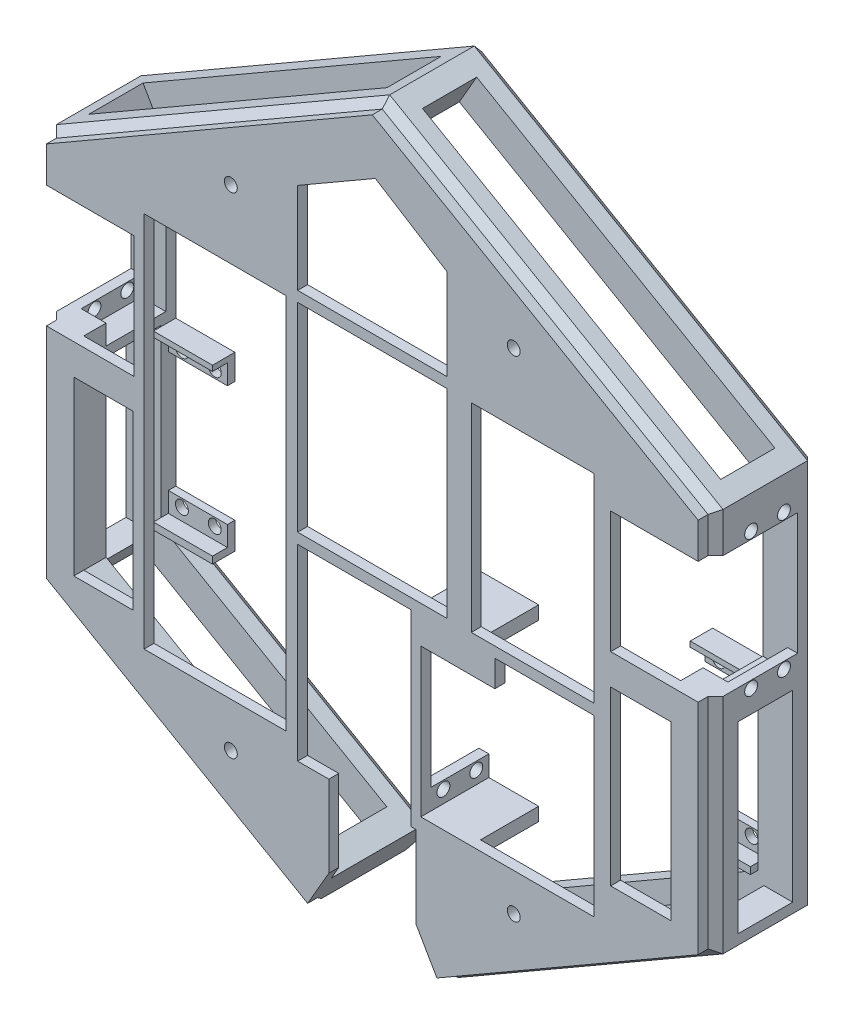
SolidWorks part; units mm, degrees
note: '?' marks a value the reader was unsure of.
material "Caoutchouc"
ref_plane "Plan de face" through (0, 0, 0) normal (0, 0, 1) x (1, 0, 0)
ref_plane "Plan de dessus" through (0, 0, 0) normal (0, 1, 0) x (1, 0, 0)
ref_plane "Plan de droite" through (0, 0, 0) normal (1, 0, 0) x (0, 0, -1)
sketch "Esquisse1" plane through (0, 0, 0) normal (0, 0, 1) x (1, 0, 0)
  line L0 (-67, -38.6825) -> (0, 0)
  line L1 (0, -8.0829) -> (60, -42.7239)
  line L2 (-67, -38.6825) -> (-67, -116.0474)
  line L3 (60, -42.7239) -> (60, -112.006)
  line L4 (67, -38.6825) -> (67, -116.0474)
  line L5 (0, 0) -> (67, -38.6825)
  line L6 (-67, -116.0474) -> (0, -154.7299)
  line L7 (0, -154.7299) -> (67, -116.0474)
  line L8 (60, -112.006) -> (0, -146.647)
  line L9 (0, -146.647) -> (-60, -112.006)
  line L10 (-60, -112.006) -> (-60, -42.7239)
  line L11 (-60, -42.7239) -> (0, -8.0829)
  dimension "D1" = 120
  dimension "D2" = 120
  dimension "D3" = 7
  dimension "D4" = 7
  dimension "D5" = 7
  dimension "D6" = 60
extrude "Boss.-Extru.1" add sketch "Esquisse1" along normal blind 20
chamfer "Chanfrein1" distance 1.5 angle 45 18 edges at (-33.5, -135.3886, 20) (-67, -77.3649, 20) (-33.5, -19.3412, 20) (33.5, -19.3412, 20) (33.5, -135.3886, 20) (67, -77.3649, 20) (-67, -77.3649, 0) (-33.5, -135.3886, 0) (33.5, -135.3886, 0) (67, -77.3649, 0) (33.5, -19.3412, 0) (-33.5, -19.3412, 0) (-30, -129.3265, 0) (30, -129.3265, 0) (60, -77.3649, 0) (30, -25.4034, 0) (-60, -77.3649, 0) (-30, -25.4034, 0)
sketch "Esquisse4" plane through (-60, 0, 0) normal (1, 0, 0) x (0, 0, -1)
  line L0 (-20, -42.7239) -> (-1.5, -42.7239) construction
  line L1 (-1.5, -112.006) -> (-1.5, -42.7239) construction
  line L2 (-3.5, -46.7239) -> (-23.5, -46.7239)
  line L3 (-3.5, -46.7239) -> (-3.5, -71.2239)
  line L4 (-3.5, -71.2239) -> (-23.5, -71.2239)
  line L9 (-23.5, -46.7239) -> (-23.5, -71.2239)
  dimension "D1" = 2
  dimension "D2" = 4
  dimension "D3" = 20
  dimension "D4" = 24.5
extrude "Enlèv. mat.-Extru.1" cut sketch "Esquisse4" against normal blind 10 and the other way through all
ref_plane "Plan1" through (0, 0, 0) normal (1, 0, 0) x (0, 0, -1)
sketch "Esquisse8" plane through (0, 0, 0) normal (-0.5, 0.866, 0) x (0, 0, 1)
  line L0 (18.5, -77.3649) -> (1.5, -77.3649) construction
  line L1 (4.55, -73.3649) -> (15.45, -73.3649)
  line L2 (4.55, -73.3649) -> (4.55, -4.15)
  line L3 (4.55, -4.15) -> (15.45, -4.15)
  line L4 (15.45, -73.3649) -> (15.45, -4.15)
  line L5 (18.5, -77.3649) -> (18.5, 0) construction
  line L6 (1.5, 0) -> (1.5, -77.3649) construction
  line L7 (18.5, 0) -> (1.5, 0) construction
  dimension "D1" = 4
  dimension "D2" = 3.05
  dimension "D3" = 3.05
  dimension "D4" = 4.15
extrude "Enlèv. mat.-Extru.3" cut sketch "Esquisse8" against normal up to surface (7 mm away) up to face at (-30, -25.4034, 10.75)
sketch "Esquisse9" plane through (0, 0, 0) normal (0.5, 0.866, 0) x (0, 0, -1)
  line L0 (-15.45, 2.075) -> (-4.55, 2.075) construction
  line L1 (-15.5, -73.3649) -> (-4.6, -73.3649)
  line L2 (-15.5, -73.3649) -> (-15.5, -4.15)
  line L3 (-15.5, -4.15) -> (-4.6, -4.15)
  line L4 (-4.6, -73.3649) -> (-4.6, -4.15)
  line L6 (-18.5, 0) -> (-1.5, 0) construction
  line L7 (-18.5, 0) -> (-18.5, -77.3649) construction
  line L8 (-18.5, -77.3649) -> (-1.5, -77.3649) construction
  dimension "D1" = 4.15
  dimension "D2" = 3
  dimension "D3" = 4
extrude "Enlèv. mat.-Extru.4" cut sketch "Esquisse9" against normal up to surface (7 mm away) up to face at (30, -25.4034, 10.75)
sketch "Esquisse10" plane through (-67, -116.0474, 0) normal (-0.5, -0.866, 0) x (0, 0, 1)
  line L0 (15.5, -4.15) -> (15.5, -73.3649) construction
  line L1 (4.5, -72.8649) -> (15.5, -72.8649)
  line L2 (4.5, -72.8649) -> (4.5, -3.65)
  line L3 (4.5, -3.65) -> (15.5, -3.65)
  line L4 (15.5, -72.8649) -> (15.5, -3.65)
  line L5 (15.5, -73.3649) -> (4.6, -73.3649) construction
  line L6 (18.5, -77.3649) -> (1.5, -77.3649) construction
  line L7 (1.5, 0) -> (1.5, -77.3649) construction
  line L8 (18.5, -77.3649) -> (18.5, 0) construction
  dimension "D1" = 4.5
  dimension "D2" = 3
  dimension "D3" = 3
sketch "Esquisse11" plane through (67, -116.0474, 0) normal (0.5, -0.866, 0) x (0, 0, -1)
  line L1 (-15.5, -4) -> (-4.5, -4)
  line L2 (-15.5, -4) -> (-15.5, -73.2149)
  line L3 (-15.5, -73.2149) -> (-4.5, -73.2149)
  line L4 (-4.5, -4) -> (-4.5, -73.2149)
  line L6 (-4.5, -79.6149) -> (-15.5, -79.6149) construction
  line L7 (-4.55, -4.15) -> (-4.55, -73.3649) construction
  line L8 (-18.5, 0) -> (-1.5, 0) construction
  line L9 (-1.5, -77.3649) -> (-1.5, 0) construction
  dimension "D1" = 4
  dimension "D2" = 3
extrude "Enlèv. mat.-Extru.5" cut sketch "Esquisse11" against normal up to surface (7 mm away) up to face at (30, -129.3265, 10.75)
extrude "Enlèv. mat.-Extru.6" cut sketch "Esquisse10" against normal up to surface (7 mm away) up to face at (-30, -129.3265, 10.75)
ref_axis "Axe1" through (93.8627, -97.9693, 20) along (-1, 0, 0)?
sketch "Esquisse13" plane through (0, 0, 20) normal (0, 0, 1) x (1, 0, 0)
  line L0 (65.5, -115.1814) -> (65.5, -39.5485)
  line L1 (65.5, -39.5485) -> (0, -1.7321)
  line L2 (0, -1.7321) -> (-65.5, -39.5485)
  line L3 (-65.5, -39.5485) -> (-65.5, -115.1814)
  line L4 (-65.5, -115.1814) -> (0, -152.9978)
  line L5 (0, -152.9978) -> (65.5, -115.1814)
extrude "Boss.-Extru.2" add sketch "Esquisse13" along normal blind 2
sketch "Esquisse18" plane through (60, 0, 0) normal (-1, 0, 0) x (0, 0, 1)
  line L0 (1.5, -112.006) -> (20, -112.006)
  line L1 (1.5, -112.006) -> (1.5, -77.3753)
  line L2 (20, -112.006) -> (20, -77.3753)
  line L3 (1.5, -77.3753) -> (20, -77.3753)
  line L5 (-25.4115, -77.3753) -> (87.8572, -77.3753) construction
  line L6 (15.5, -42.7446) -> (4.6, -42.7446) construction
extrude "Boss.-Extru.5" add sketch "Esquisse18" along normal blind 30
mirror "Symétrie5" about plane through (0, 0, 0) normal (1, 0, 0) of "Boss.-Extru.5"
sketch "Esquisse20" plane through (0, 0, 20) normal (0, 0, -1) x (-1, 0, 0)
  line L1 (-30, -77.3753) -> (-60, -77.3753)
  line L2 (-30, -77.3753) -> (-30, -112.006)
  line L3 (-30, -112.006) -> (-60, -112.006)
  line L4 (-60, -77.3753) -> (-60, -112.006)
extrude "Enlèv. mat.-Extru.9" cut sketch "Esquisse20" against normal blind 10 and the other way blind 14
sketch "Esquisse19" plane through (0, 0, 1.5) normal (0, 0, -1) x (-1, 0, 0)
  line L0 (-48.116, -82.6623) -> (-59.8, -82.6623) construction
  line L1 (-47.916, -82.4623) -> (-60, -82.4623)
  line L2 (-47.916, -82.4623) -> (-47.916, -106.6113)
  line L3 (-47.916, -106.6113) -> (-60, -106.6113)
  line L4 (-60, -82.4623) -> (-60, -106.6113)
  line L5 (-59.8, -106.4113) -> (-48.116, -106.4113) construction
  line L6 (-59.8, -90.0401) -> (-59.8, -106.4113) construction
  line L7 (-48.116, -90.2225) -> (-48.116, -106.4113) construction
  dimension "D1" = 0.2
  dimension "D2" = 0.2
  dimension "D3" = 0.2
  dimension "D4" = 0.2
extrude "Enlèv. mat.-Extru.8" cut sketch "Esquisse19" against normal up to next
sketch "Esquisse21" plane through (0, 0, 1.5) normal (0, 0, -1) x (-1, 0, 0)
  line L0 (-42.5871, -94.5368) -> (-95.367, -94.5368) construction
  line L1 (-47.916, -82.4623) -> (-60, -82.4623) construction
  line L2 (-60, -106.6113) -> (-47.916, -106.6113) construction
  circle A0 centre (-50.656, -80.8843) radius 1.3
  circle A1 centre (-57.26, -80.8843) radius 1.3
  circle A2 centre (-57.26, -80.8843) radius 1.016 construction
  circle A3 centre (-50.656, -108.1893) radius 1.3
  circle A4 centre (-57.26, -108.1893) radius 1.3
  circle A6 centre (-50.656, -80.8843) radius 1.016 construction
  dimension "D1" = 2.6
sketch "Esquisse22" plane through (30, 0, 0) normal (-1, 0, 0) x (0, 0, 1)
  line L1 (6, -112.006) -> (1.5, -112.006)
  line L2 (6, -112.006) -> (6, -77.3753)
  line L3 (6, -77.3753) -> (1.5, -77.3753)
  line L4 (1.5, -112.006) -> (1.5, -77.3753)
extrude "Enlèv. mat.-Extru.10" cut sketch "Esquisse22" against normal up to surface (17.916 mm away) up to face at (47.916, -94.5368, 3.75)
sketch "Esquisse23" plane through (30, 0, 0) normal (1, 0, 0) x (0, 0, -1)
  line L1 (-20, -112.006) -> (-22, -112.006)
  line L2 (-20, -112.006) -> (-20, -77.3753)
  line L3 (-20, -77.3753) -> (-22, -77.3753)
  line L4 (-22, -112.006) -> (-22, -77.3753)
extrude "Boss.-Extru.6" add sketch "Esquisse23" along normal up to surface (77.916 mm away)
extrude "Enlèv. mat.-Extru.11" cut sketch "Esquisse21" against normal up to next
sketch "Esquisse24" plane through (0, 0, 6) normal (0, 0, 1) x (1, 0, 0)
  line L0 (48.9054, -94.5368) -> (93.5273, -94.5368) construction
  line L1 (60, -82.4623) -> (60, -77.3753) construction
  line L2 (47.916, -82.4623) -> (60, -82.4623)
  line L3 (47.916, -82.4623) -> (47.916, -78.4623)
  line L4 (47.916, -78.4623) -> (60, -78.4623)
  line L5 (60, -82.4623) -> (60, -78.4623)
  line L6 (60, -106.6113) -> (47.916, -106.6113) construction
  line L7 (47.916, -106.6113) -> (60, -106.6113)
  line L8 (60, -106.6113) -> (60, -110.6113)
  line L9 (47.916, -110.6113) -> (60, -110.6113)
  line L10 (47.916, -106.6113) -> (47.916, -110.6113)
  dimension "D1" = 4
extrude "Enlèv. mat.-Extru.12" cut sketch "Esquisse24" against normal blind 3
mirror "Symétrie13" about plane through (0, 0, 0) normal (1, 0, 0) of "Enlèv. mat.-Extru.9", "Boss.-Extru.6", "Enlèv. mat.-Extru.11", "Enlèv. mat.-Extru.12", "Enlèv. mat.-Extru.8"
sketch "Esquisse25" plane through (-30, 0, 0) normal (1, 0, 0) x (0, 0, -1)
  line L0 (-1.5, -112.006) -> (-6, -112.006) construction
  line L1 (-6, -112.006) -> (-1.5, -112.006)
  line L2 (-6, -112.006) -> (-6, -77.3753)
  line L3 (-6, -77.3753) -> (-1.5, -77.3753)
  line L4 (-1.5, -112.006) -> (-1.5, -77.3753)
  line L5 (-6, -112.006) -> (-6, -77.3753) construction
  line L6 (-6, -77.3753) -> (-1.5, -77.3753) construction
extrude "Enlèv. mat.-Extru.13" cut sketch "Esquisse25" against normal up to surface (18.116 mm away)
sketch "Esquisse26" plane through (-30, 0, 0) normal (-1, 0, 0) x (0, 0, 1)
  line L1 (22, -112.006) -> (20, -112.006)
  line L2 (22, -112.006) -> (22, -77.3753)
  line L3 (22, -77.3753) -> (20, -77.3753)
  line L4 (20, -112.006) -> (20, -77.3753)
  line L6 (20, -112.006) -> (20, -77.3753) construction
  line L7 (22, -112.006) -> (22, -77.3753) construction
extrude "Boss.-Extru.7" add sketch "Esquisse26" along normal up to surface (18.116 mm away)
sketch "Esquisse27" plane through (67, 0, 0) normal (1, 0, 0) x (0, 0, -1)
  line L0 (-41.0609, -58.9739) -> (19.2383, -58.9739) construction
  line L3 (-3.5, -46.7239) -> (-18.5, -46.7239) construction
  line L4 (-18.5, -71.2239) -> (-3.5, -71.2239) construction
  circle A0 centre (-12.844, -45.2969) radius 1.3
  circle A2 centre (-6.24, -45.2969) radius 1.3
  circle A3 centre (-6.24, -45.2969) radius 1.016 construction
  circle A5 centre (-12.844, -45.2969) radius 1.016 construction
  circle A6 centre (-6.24, -72.6509) radius 1.3
  circle A8 centre (-12.844, -72.6509) radius 1.3
  dimension "D1" = 2.6
extrude "Enlèv. mat.-Extru.14" cut sketch "Esquisse27" against normal up to next
mirror "Symétrie14" about plane through (0, 0, 0) normal (1, 0, 0) of "Enlèv. mat.-Extru.14"
sketch "Esquisse28" plane through (0, 0, 22) normal (0, 0, 1) x (1, 0, 0)
  line L0 (65.5, -115.1814) -> (65.5, -39.5485) construction
  line L1 (65.5, -71.2239) -> (47.916, -71.2239)
  line L2 (65.5, -71.2239) -> (65.5, -46.7239)
  line L3 (65.5, -46.7239) -> (47.916, -46.7239)
  line L4 (47.916, -71.2239) -> (47.916, -46.7239)
  line L5 (65.5, -46.7239) -> (67, -46.7239) construction
  line L6 (67, -71.2239) -> (65.5, -71.2239) construction
  line L7 (47.916, -112.006) -> (47.916, -77.3753) construction
  line L8 (0, -227.3308) -> (0, 88.9746) construction
  line L9 (-65.5, -71.2239) -> (-65.5, -46.7239)
  line L10 (-65.5, -71.2239) -> (-47.916, -71.2239)
  line L11 (-65.5, -46.7239) -> (-47.916, -46.7239)
  line L12 (-47.916, -71.2239) -> (-47.916, -46.7239)
extrude "Enlèv. mat.-Extru.15" cut sketch "Esquisse28" against normal up to next
sketch "Esquisse29" plane through (60, 0, 0) normal (-1, 0, 0) x (0, 0, 1)
  line L1 (3.5, -46.7239) -> (15.5113, -46.7239)
  line L2 (3.5, -46.7239) -> (3.5, -42.7239)
  line L3 (3.5, -42.7239) -> (15.5113, -42.7239)
  line L4 (15.5113, -46.7239) -> (15.5113, -42.7239)
  line L5 (-8.7621, -58.9739) -> (44.89, -58.9739) construction
  line L6 (20, -71.2239) -> (3.5, -71.2239) construction
  line L7 (3.5, -71.2239) -> (15.5113, -71.2239)
  line L8 (15.5113, -71.2239) -> (15.5113, -75.2239)
  line L9 (3.5, -71.2239) -> (3.5, -75.2239)
  line L10 (3.5, -75.2239) -> (15.5113, -75.2239)
  dimension "D1" = 4
extrude "Enlèv. mat.-Extru.16" cut sketch "Esquisse29" against normal blind 5
mirror "Symétrie15" about plane through (0, 0, 0) normal (1, 0, 0) of "Enlèv. mat.-Extru.16"
sketch "Esquisse30" plane through (0, 0, 22) normal (0, 0, 1) x (1, 0, 0)
  line L0 (7.7559, -87.6779) -> (7.7559, -90.9959) construction
  line L1 (34.6469, -83.9959) -> (7.7559, -83.9959)
  line L2 (34.6469, -83.9959) -> (34.6469, -121.7449)
  line L3 (34.6469, -121.7449) -> (7.7559, -121.7449)
  line L4 (7.7559, -83.9959) -> (7.7559, -121.7449)
  line L5 (7.7559, -114.7449) -> (24.6469, -114.7449) construction
  line L6 (24.6469, -90.9959) -> (7.7559, -90.9959) construction
  line L7 (24.6469, -114.7449) -> (24.6469, -90.9959) construction
  dimension "D1" = 7
  dimension "D2" = 7
  dimension "D3" = 10
extrude "Boss.-Extru.8" add sketch "Esquisse30" against normal up to surface (13.684 mm away)
sketch "Esquisse31" plane through (34.6469, 0, 0) normal (1, 0, 0) x (0, 0, -1)
  line L1 (-20, -121.7449) -> (-8.316, -121.7449)
  line L2 (-20, -121.7449) -> (-20, -83.9959)
  line L3 (-20, -83.9959) -> (-8.316, -83.9959)
  line L4 (-8.316, -121.7449) -> (-8.316, -83.9959)
extrude "Enlèv. mat.-Extru.18" cut sketch "Esquisse31" against normal up to surface (10 mm away)
sketch "Esquisse32" plane through (0, 0, 8.316) normal (0, 0, -1) x (-1, 0, 0)
  line L0 (-24.6469, -121.7449) -> (-24.6469, -83.9959) construction
  line L1 (-24.6469, -114.9449) -> (-7.7559, -114.9449)
  line L2 (-24.6469, -114.9449) -> (-24.6469, -90.7959)
  line L3 (-24.6469, -90.7959) -> (-7.7559, -90.7959)
  line L4 (-7.7559, -114.9449) -> (-7.7559, -90.7959)
  line L5 (-7.7559, -83.9959) -> (-7.7559, -121.7449) construction
  line L6 (-24.6469, -90.9959) -> (-7.7559, -90.9959) construction
  line L7 (-7.7559, -114.7449) -> (-24.6469, -114.7449) construction
  dimension "D1" = 0.2
  dimension "D2" = 0.2
extrude "Enlèv. mat.-Extru.19" cut sketch "Esquisse32" against normal up to surface (11.684 mm away) up to face at (16.2014, -102.8704, 20)
sketch "Esquisse33" plane through (0, 0, 8.316) normal (0, 0, -1) x (-1, 0, 0)
  line L0 (-24.6469, -114.9449) -> (-7.7559, -114.9449) construction
  line L1 (-24.6469, -121.7449) -> (-9.7559, -121.7449)
  line L2 (-24.6469, -121.7449) -> (-24.6469, -114.9449)
  line L3 (-24.6469, -114.9449) -> (-9.7559, -114.9449)
  line L4 (-9.7559, -121.7449) -> (-9.7559, -114.9449)
  line L5 (-7.7559, -114.9449) -> (-7.7559, -121.7449) construction
  line L6 (-32.4861, -102.8704) -> (32.4137, -102.8704) construction
  line L7 (-7.7559, -90.7959) -> (-24.6469, -90.7959) construction
  line L8 (-24.6469, -83.9959) -> (-24.6469, -90.7959)
  line L9 (-24.6469, -90.7959) -> (-9.7559, -90.7959)
  line L10 (-9.7559, -83.9959) -> (-9.7559, -90.7959)
  line L11 (-24.6469, -83.9959) -> (-9.7559, -83.9959)
  line L12 (-24.6469, -83.9959) -> (-7.7559, -83.9959) construction
  line L13 (-7.7559, -121.7449) -> (-24.6469, -121.7449) construction
  line L14 (-24.6469, -90.7959) -> (-24.6469, -83.9959) construction
  line L15 (-24.6469, -121.7449) -> (-24.6469, -114.9449) construction
  dimension "D1" = 2
extrude "Enlèv. mat.-Extru.20" cut sketch "Esquisse33" against normal up to surface (11.684 mm away) up to face at (16.2014, -87.3959, 20)
sketch "Esquisse34" plane through (9.7559, 0, 0) normal (1, 0, 0) x (0, 0, -1)
  line L0 (-20, -121.7449) -> (-20, -114.9449) construction
  line L1 (-8.316, -121.7449) -> (-20, -121.7449)
  line L2 (-8.316, -121.7449) -> (-8.316, -119.0629)
  line L3 (-8.316, -119.0629) -> (-20, -119.0629)
  line L4 (-20, -121.7449) -> (-20, -119.0629)
  line L5 (-19, -119.0629) -> (-9.316, -119.0629) construction
  line L6 (42.2371, -102.8704) -> (-69.3364, -102.8704) construction
  line L7 (-20, -114.9449) -> (-8.316, -114.9449) construction
  line L8 (-20, -90.7959) -> (-8.316, -90.7959) construction
  line L9 (-8.316, -86.6779) -> (-20, -86.6779)
  line L10 (-20, -83.9959) -> (-20, -86.6779)
  line L11 (-8.316, -83.9959) -> (-20, -83.9959)
  line L12 (-8.316, -83.9959) -> (-8.316, -86.6779)
extrude "Boss.-Extru.9" add sketch "Esquisse34" along normal blind 10
sketch "Esquisse35" plane through (7.7559, 0, 0) normal (-1, 0, 0) x (0, 0, 1)
  line L0 (-20.2081, -102.8704) -> (49.4608, -102.8704) construction
  line L1 (20, -90.7959) -> (8.316, -90.7959) construction
  line L2 (20, -114.9449) -> (8.316, -114.9449) construction
  circle A0 centre (17.46, -116.5229) radius 1.3
  circle A1 centre (10.856, -116.5229) radius 1.3
  circle A3 centre (10.856, -116.5229) radius 1.016 construction
  circle A4 centre (17.46, -116.5229) radius 1.016 construction
  circle A5 centre (17.46, -89.2179) radius 1.3
  circle A6 centre (10.856, -89.2179) radius 1.3
  dimension "D1" = 2.6
extrude "Enlèv. mat.-Extru.21" cut sketch "Esquisse35" against normal blind 10
sketch "Esquisse36" plane through (0, 0, 20) normal (0, 0, -1) x (-1, 0, 0)
  line L0 (-19.7559, -119.0629) -> (-9.7559, -119.0629) construction
  line L1 (-9.7559, -89.3177) -> (-24.6469, -89.3177)
  line L2 (-9.7559, -89.3177) -> (-9.7559, -119.0629)
  line L3 (-9.7559, -119.0629) -> (-24.6469, -119.0629)
  line L4 (-24.6469, -89.3177) -> (-24.6469, -119.0629)
  line L5 (-24.6469, -114.7449) -> (-24.6469, -90.9959) construction
  line L7 (-9.7559, -119.0629) -> (-9.7559, -114.9449) construction
extrude "Enlèv. mat.-Extru.22" cut sketch "Esquisse36" against normal blind 10
sketch "Esquisse37" plane through (0, 0, 22) normal (0, 0, 1) x (1, 0, 0)
  line L0 (-106.0914, -77.3649) -> (143.3828, -77.3649) construction
  line L1 (0, 60.915) -> (0, -188.0892) construction
  line L2 (104.4061, -42.7239) -> (-106.2979, -42.7239) construction
  line L3 (143.3828, -112.006) -> (-139.6208, -112.006) construction
  circle A0 centre (28.4338, -28.1141) radius 1.3
  circle A1 centre (-28.4338, -28.1141) radius 1.3
  circle A2 centre (28.4338, -126.6157) radius 1.3
  circle A3 centre (-28.4338, -126.6157) radius 1.3
  dimension "D1" = 2.6
  dimension "D2" = 34.641
  dimension "D3" = 34.641
extrude "Enlèv. mat.-Extru.23" cut sketch "Esquisse37" against normal blind 5
sketch "Esquisse38" plane through (0, 0, 20) normal (0, 0, -1) x (-1, 0, 0)
  line L0 (-15, -81.8808) -> (-15, -41.8808)
  line L1 (-15, -81.8808) -> (15, -81.8808)
  line L2 (-15, -41.8808) -> (15, -41.8808)
  line L3 (15, -81.8808) -> (15, -41.8808)
  line L5 (0, 45.2004) -> (0, -169.1986) construction
  dimension "D1" = 15
  dimension "D2" = 40
extrude "Enlèv. mat.-Extru.24" cut sketch "Esquisse38" against normal up to next
sketch "Esquisse39" plane through (-67, 0, 0) normal (-1, 0, 0) x (0, 0, 1)
  line L0 (15.5, -114.0474) -> (15.5, -77.1419)
  line L1 (15.5, -114.0474) -> (4.5, -114.0474)
  line L2 (15.5, -77.1419) -> (4.5, -77.1419)
  line L3 (4.5, -114.0474) -> (4.5, -77.1419)
  line L4 (15.5, -152.4799) -> (15.5, -117.8724) construction
  line L5 (4.5, -117.8724) -> (4.5, -152.4799) construction
  line L6 (18.5, -116.0474) -> (1.5, -116.0474) construction
  line L7 (14.384, -75.1419) -> (4.7, -75.1419) construction
  dimension "D1" = 2
  dimension "D2" = 2
extrude "Enlèv. mat.-Extru.25" cut sketch "Esquisse39" against normal up to surface (7 mm away) up to face at (-60, -86.0074, 9.0692)
sketch "Esquisse40" plane through (67, 0, 0) normal (1, 0, 0) x (0, 0, -1)
  line L0 (-15.5, -118.0474) -> (-15.5, -152.6549) construction
  line L1 (-15.5, -114.0474) -> (-4.5, -114.0474)
  line L2 (-15.5, -114.0474) -> (-15.5, -77.1419)
  line L3 (-15.5, -77.1419) -> (-4.5, -77.1419)
  line L4 (-4.5, -114.0474) -> (-4.5, -77.1419)
  line L5 (-4.5, -152.6549) -> (-4.5, -118.0474) construction
  line L6 (-18.5, -116.0474) -> (-1.5, -116.0474) construction
  line L7 (-14.384, -75.1419) -> (-4.7, -75.1419) construction
  dimension "D1" = 2
  dimension "D2" = 2
extrude "Enlèv. mat.-Extru.26" cut sketch "Esquisse40" against normal up to surface (7 mm away) up to face at (60, -86.0074, 9.0692)
sketch "Esquisse41" plane through (67, -116.0474, 0) normal (0.5, -0.866, 0) x (0.866, 0.5, 0)
  line L1 (-76.4989, 22) -> (-61.4989, 22)
  line L2 (-76.4989, 22) -> (-76.4989, 0)
  line L3 (-76.4989, 0) -> (-61.4989, 0)
  line L4 (-61.4989, 22) -> (-61.4989, 0)
  dimension "D1" = 15
extrude "Enlèv. mat.-Extru.27" cut sketch "Esquisse41" against normal blind 10
sketch "Esquisse42" plane through (-67, -116.0474, 0) normal (-0.5, -0.866, 0) x (0.866, -0.5, 0)
  line L1 (76.4989, 22) -> (61.4989, 22)
  line L2 (76.4989, 22) -> (76.4989, 0)
  line L3 (76.4989, 0) -> (61.4989, 0)
  line L4 (61.4989, 22) -> (61.4989, 0)
  dimension "D1" = 15
extrude "Enlèv. mat.-Extru.28" cut sketch "Esquisse42" against normal blind 10
sketch "Esquisse43" plane through (-67, -116.0474, 0) normal (-0.5, -0.866, 0) x (0.866, -0.5, 0)
  line L1 (74.7929, 20.6726) -> (79.1527, 20.6726)
  line L2 (74.7929, 20.6726) -> (74.7929, -0.8392)
  line L3 (74.7929, -0.8392) -> (79.1527, -0.8392)
  line L4 (79.1527, 20.6726) -> (79.1527, -0.8392)
extrude "Enlèv. mat.-Extru.29" cut sketch "Esquisse43" against normal blind 10
sketch "Esquisse44" plane through (0, 0, 15.5) normal (0, 0, -1) x (-1, 0, 0)
  line L0 (-13.7404, -146.7969) -> (-10.2404, -140.7347)
  line L1 (-13.7404, -146.7969) -> (-18.0705, -144.2969)
  line L2 (-10.2404, -140.7347) -> (-14.5705, -138.2347)
  line L3 (-18.0705, -144.2969) -> (-14.5705, -138.2347)
  line L4 (13.7404, -146.7969) -> (10.2404, -140.7347)
  line L5 (13.7404, -146.7969) -> (18.0705, -144.2969)
  line L6 (10.2404, -140.7347) -> (14.5705, -138.2347)
  line L7 (18.0705, -144.2969) -> (14.5705, -138.2347)
  dimension "D1" = 5
  dimension "D2" = 5
extrude "Boss.-Extru.10" add sketch "Esquisse44" along normal up to next
sketch "Esquisse45" plane through (0, 0, 20) normal (0, 0, -1) x (-1, 0, 0)
  line L1 (-44.5264, -41.8808) -> (-19.9041, -41.8808)
  line L2 (-44.5264, -41.8808) -> (-44.5264, -81.8808)
  line L3 (-44.5264, -81.8808) -> (-19.9041, -81.8808)
  line L4 (-19.9041, -41.8808) -> (-19.9041, -81.8808)
  line L5 (17.3381, -41.8808) -> (45.8835, -41.8808)
  line L6 (17.3381, -41.8808) -> (17.3381, -117.6707)
  line L7 (17.3381, -117.6707) -> (45.8835, -117.6707)
  line L8 (45.8835, -41.8808) -> (45.8835, -117.6707)
  line L9 (-24.6469, -83.9959) -> (-44.5264, -83.9959)
  line L10 (-24.6469, -83.9959) -> (-24.6469, -119.0629)
  line L11 (-24.6469, -119.0629) -> (-44.5264, -119.0629)
  line L12 (-44.5264, -83.9959) -> (-44.5264, -119.0629)
  line L14 (-15, -21.5166) -> (-15, -39.7918)
  line L15 (-15, -39.7918) -> (15, -39.7918)
  line L16 (15, -21.5166) -> (15, -39.7918)
  line L17 (15, -83.9959) -> (-7.7559, -83.9959)
  line L18 (15, -83.9959) -> (15, -121.7449)
  line L19 (8.7404, -121.7449) -> (15, -121.7449)
  line L20 (-8.7404, -121.7449) -> (-7.7559, -121.7449)
  line L21 (-19.7559, -83.9959) -> (-7.7559, -83.9959) construction
  line L22 (-15, -41.8808) -> (-15, -81.8808) construction
  line L23 (15, -81.8808) -> (15, -41.8808) construction
  line L24 (15, -41.8808) -> (-15, -41.8808) construction
  line L25 (-15, -81.8808) -> (15, -81.8808) construction
  line L26 (-15, -21.5166) -> (-0.6112, -12.5034)
  line L27 (-0.6112, -12.5034) -> (15, -21.5166)
  line L28 (0, -8.0829) -> (60, -42.7239) construction
  line L29 (-8.7404, -138.1366) -> (0, -143.1829)
  line L30 (-8.7404, -121.7449) -> (-8.7404, -138.1366)
  line L31 (-7.7559, -121.7449) -> (-7.7559, -83.9959)
  line L33 (8.7404, -138.1366) -> (8.7404, -121.7449)
  line L34 (0, -143.1829) -> (8.7404, -138.1366)
extrude "Enlèv. mat.-Extru.33" cut sketch "Esquisse45" against normal blind 10
